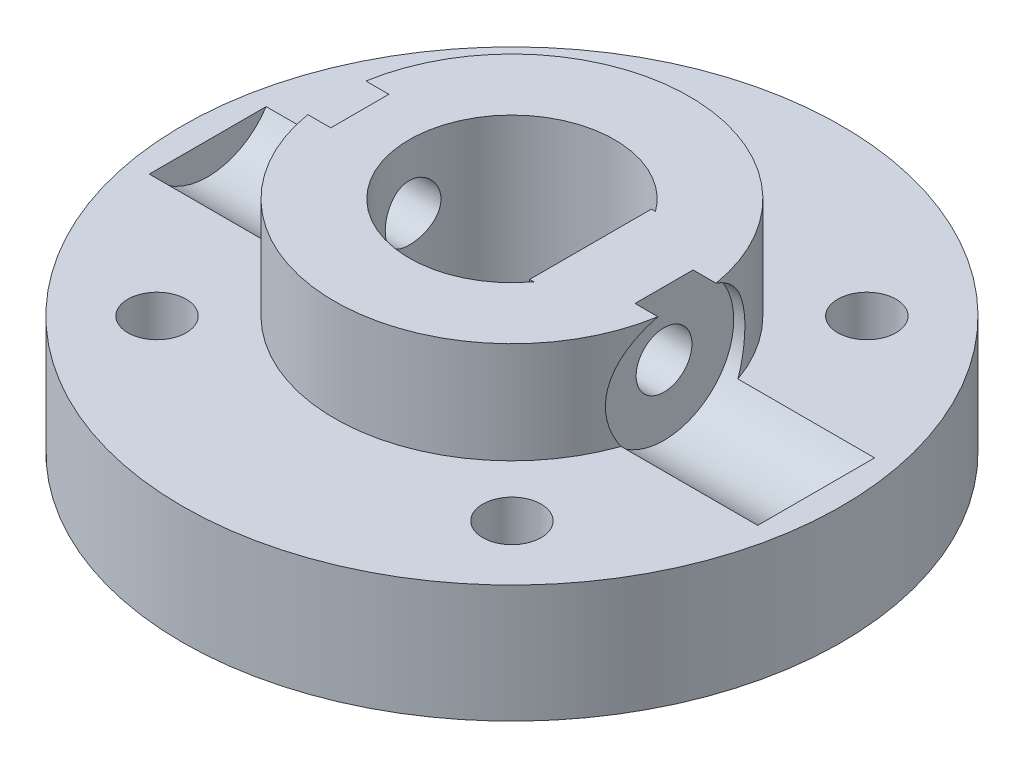
SolidWorks part; units mm, degrees
ref_plane "Front Plane" through (0, 0, 0) normal (0, 0, 1) x (1, 0, 0)
ref_plane "Top Plane" through (0, 0, 0) normal (0, 1, 0) x (1, 0, 0)
ref_plane "Right Plane" through (0, 0, 0) normal (1, 0, 0) x (0, 0, -1)
sketch "Stock_horn_drive_flange_profile" plane through (0, 0, 0) normal (0, 1, 0) x (1, 0, 0)
  circle A0 centre (0, 0) radius 13
  circle A1 centre (0, 0) radius 4.05
  dimension "D1" = 26
  dimension "D2" = 8.1
extrude "Stock_horn_drive_flange" add sketch "Stock_horn_drive_flange_profile" along normal blind 3 from offset 41
sketch "D_coupling_ring_profile" plane through (0, 0, 0) normal (0, 1, 0) x (1, 0, 0)
  circle A0 centre (0, 0) radius 7
  circle A1 centre (0, 0) radius 4.05
  dimension "D1" = 14
  dimension "D2" = 8.1
extrude "D_coupling_ring" add sketch "D_coupling_ring_profile" along normal blind 4 from offset 44
sketch "D_key_land_profile" plane through (0, 0, 0) normal (0, 1, 0) x (1, 0, 0)
  line L1 (3.1, -2.4) -> (6, -2.4)
  line L2 (3.1, -2.4) -> (3.1, 2.4)
  line L3 (3.1, 2.4) -> (6, 2.4)
  line L4 (6, -2.4) -> (6, 2.4)
  dimension "D1" = 2.9
  dimension "D2" = 4.8
extrude "D_key_land" add sketch "D_key_land_profile" along normal blind 4 from offset 44
sketch "Captured_horn_key_boss_profile" plane through (0, 0, 0) normal (0, 1, 0) x (1, 0, 0)
  circle A0 centre (0, 0) radius 13
  dimension "D1" = 26
extrude "Captured_horn_key_boss" add sketch "Captured_horn_key_boss_profile" along normal blind 1.65 from offset 39.35
sketch "Stock_horn_pocket_Hub" plane through (0, 0, 0) normal (0, 1, 0) x (1, 0, 0)
  circle A0 centre (0, 0) radius 3.55
  dimension "D1" = 7.1
extrude "Key_pocket_Hub" cut sketch "Stock_horn_pocket_Hub" along normal blind 1.65 from offset 39.35
sketch "Stock_horn_pocket_Horizontal" plane through (0, 0, 0) normal (0, 1, 0) x (1, 0, 0)
  line L1 (-8.15, -2.1) -> (8.15, -2.1)
  line L2 (-8.15, -2.1) -> (-8.15, 2.1)
  line L3 (-8.15, 2.1) -> (8.15, 2.1)
  line L4 (8.15, -2.1) -> (8.15, 2.1)
  dimension "D1" = 16.3
  dimension "D2" = 4.2
extrude "Key_pocket_Horizontal" cut sketch "Stock_horn_pocket_Horizontal" along normal blind 1.65 from offset 39.35
sketch "Stock_horn_pocket_Vertical" plane through (0, 0, 0) normal (0, 1, 0) x (1, 0, 0)
  line L1 (-2.1, -8.15) -> (2.1, -8.15)
  line L2 (-2.1, -8.15) -> (-2.1, 8.15)
  line L3 (-2.1, 8.15) -> (2.1, 8.15)
  line L4 (2.1, -8.15) -> (2.1, 8.15)
  dimension "D1" = 4.2
  dimension "D2" = 16.3
extrude "Key_pocket_Vertical" cut sketch "Stock_horn_pocket_Vertical" along normal blind 1.65 from offset 39.35
sketch "Stock_horn_pocket_Rounded_tips" plane through (0, 0, 0) normal (0, 1, 0) x (1, 0, 0)
  circle A0 centre (8.15, 0) radius 2.1
  circle A1 centre (-8.15, 0) radius 2.1
  circle A2 centre (0, 8.15) radius 2.1
  circle A3 centre (0, -8.15) radius 2.1
  dimension "D1" = 4.2
  dimension "D2" = 4.2
  dimension "D3" = 4.2
  dimension "D4" = 4.2
extrude "Key_pocket_Rounded_tips" cut sketch "Stock_horn_pocket_Rounded_tips" along normal blind 1.65 from offset 39.35
sketch "Unmodified_horn_capture_M2_profile" plane through (0, 0, 0) normal (0, 1, 0) x (1, 0, 0)
  circle A0 centre (7, 7) radius 1.15
  circle A1 centre (-7, 7) radius 1.15
  circle A2 centre (-7, -7) radius 1.15
  circle A3 centre (7, -7) radius 1.15
  dimension "D1" = 2.3
  dimension "D2" = 2.3
  dimension "D3" = 2.3
  dimension "D4" = 2.3
extrude "Unmodified_horn_capture_M2" cut sketch "Unmodified_horn_capture_M2_profile" along normal through all from offset 50 offset against normal yes
sketch "Horn_center_hub_clearance" plane through (0, 0, 0) normal (0, 1, 0) x (1, 0, 0)
  circle A0 centre (0, 0) radius 4
  dimension "D1" = 8
extrude "Hub_clearance_in_key_boss_only" cut sketch "Horn_center_hub_clearance" along normal blind 1.65 from offset 39.35
sketch "Yaw_positive_retention_crossbolt_profile" plane through (0, 0, 0) normal (1, 0, 0) x (0, 0, -1)
  circle A0 centre (0, 45.5) radius 1.1
  dimension "D1" = 2.2
extrude "Yaw_positive_retention_crossbolt" cut sketch "Yaw_positive_retention_crossbolt_profile" along normal through all from offset 10 offset against normal yes
sketch "Crossbolt_flat_seat_-12" plane through (0, 0, 0) normal (1, 0, 0) x (0, 0, -1)
  circle A0 centre (0, 45.5) radius 2.75
  dimension "D1" = 5.5
extrude "Crossbolt_flat_seat_cut_-12" cut sketch "Crossbolt_flat_seat_-12" along normal blind 6 from offset 12 offset against normal yes
sketch "Crossbolt_flat_seat_6" plane through (0, 0, 0) normal (1, 0, 0) x (0, 0, -1)
  circle A0 centre (0, 45.5) radius 2.75
  dimension "D1" = 5.5
extrude "Crossbolt_flat_seat_cut_6" cut sketch "Crossbolt_flat_seat_6" along normal blind 6 from offset 6
